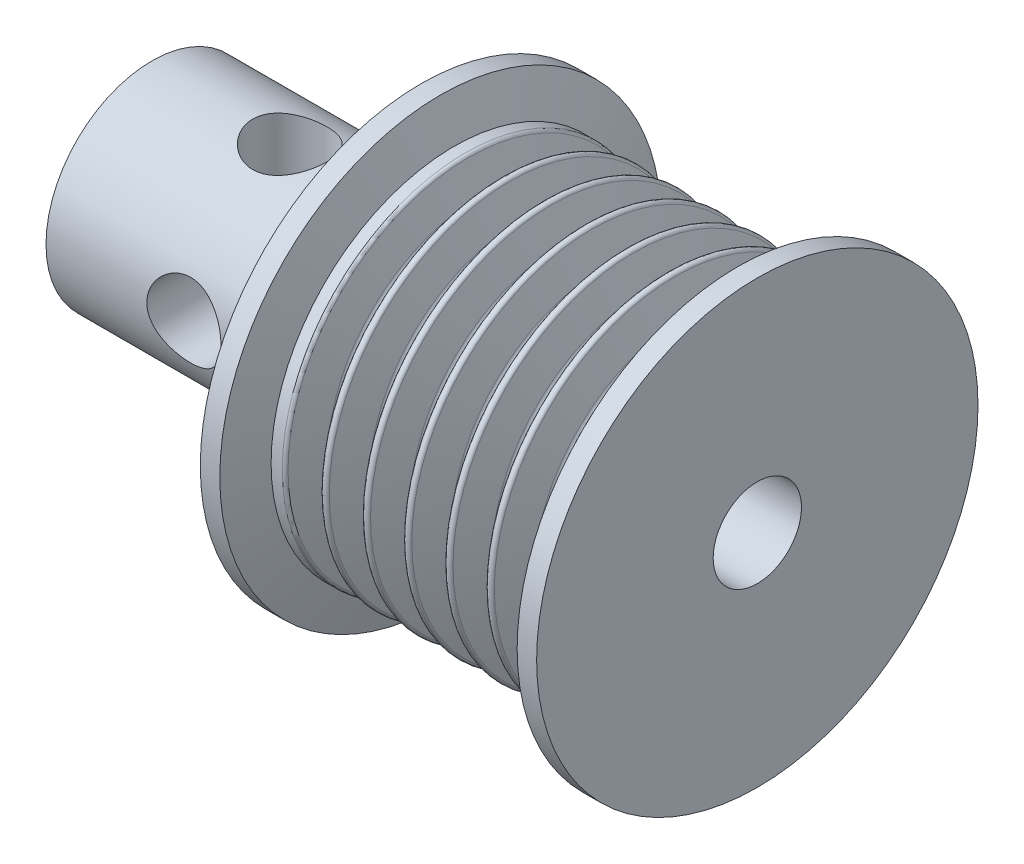
SolidWorks part; units mm, degrees
material "6061-T6 (SS)"
ref_plane "Front Plane" through (0, 0, 0) normal (0, 0, 1) x (1, 0, 0)
ref_plane "Top Plane" through (0, 0, 0) normal (0, 1, 0) x (1, 0, 0)
ref_plane "Right Plane" through (0, 0, 0) normal (1, 0, 0) x (0, 0, -1)
sketch "Sketch1" plane through (0, 0, 0) normal (0, 0, 1) x (1, 0, 0)
  line L0 (0, 0) -> (0, 2.5) construction
  line L1 (0, 2.5) -> (34.29, 2.5)
  line L2 (34.29, 2.5) -> (34.29, 12.5)
  line L3 (34.29, 12.5) -> (15.24, 12.5)
  line L4 (15.24, 12.5) -> (15.24, 6)
  line L5 (0, 0) -> (13.5959, 0) construction
  line L8 (15.24, 6) -> (0, 6)
  line L9 (0, 6) -> (0, 2.5)
  dimension "D1" = 25
  dimension "D2" = 5
  dimension "D3" = 19.05
  dimension "D6" = 12
  dimension "D7" = 15.24
revolve "Revolve1" add sketch "Sketch1" angle 360 about L5
sketch "Sketch2" plane through (0, 0, 0) normal (0, 0, 1) x (1, 0, 0)
  line L0 (29.4386, 12.5) -> (29.4386, 10.3699)
  line L1 (15.24, 6) -> (15.24, -6) construction
  line L2 (29.6295, 10.2362) -> (30.2251, 8.5999)
  line L3 (30.9889, 8.5999) -> (31.5845, 10.2362)
  line L4 (31.7754, 10.3699) -> (31.7754, 12.5)
  line L5 (31.7754, 12.5) -> (29.4386, 12.5)
  line L6 (29.4386, 11.43) -> (31.7754, 11.43) construction
  line L7 (15.24, 0) -> (34.29, 0) construction
  line L8 (29.6295, 10.2362) -> (31.5845, 10.2362) construction
  line L9 (29.4386, 12.5) -> (27.1018, 12.5) construction
  line L10 (34.29, 12.5) -> (15.24, 12.5) construction
  line L11 (27.1018, 12.5) -> (24.765, 12.5) construction
  line L13 (24.765, 0) -> (24.765, 12.5) construction
  line L15 (34.29, -12.5) -> (34.29, 12.5) construction
  arc A0 (29.4386, 10.3699) -> (29.6295, 10.2362) centre (29.4386, 10.1667) cw
  arc A1 (30.2251, 8.5999) -> (30.9889, 8.5999) centre (30.607, 8.7389) ccw
  arc A2 (31.5845, 10.2362) -> (31.7754, 10.3699) centre (31.7754, 10.1667) cw
  dimension "D1" = 0.4064
  dimension "D5" = 0.2032
  dimension "D2" = 2.3368
  dimension "D4" = 1.1938
  dimension "D6" = 40
  dimension "D7" = 11.43
revolve "Cut-Revolve1" cut sketch "Sketch2" angle 360 about L7
pattern_linear "LPattern1" count 6 spacing 2.3368 along (-1, 0, 0) of "Cut-Revolve1"
sketch "Sketch3" plane through (0, 0, 0) normal (0, 0, 1) x (1, 0, 0)
  line L0 (31.7754, 12.5) -> (33.1857, 12.5)
  line L1 (34.29, 12.5) -> (31.7754, 12.5) construction
  line L2 (33.1857, 12.5) -> (32.4104, 10.3699)
  line L3 (32.4104, 10.3699) -> (31.7754, 10.3699)
  line L4 (31.7754, 12.5) -> (31.7754, -12.5) construction
  line L5 (31.7754, 10.3699) -> (31.7754, 12.5)
  line L6 (31.7754, 10.3699) -> (31.7754, -10.3699) construction
  line L7 (30.607, 8.3325) -> (30.607, 11.4458) construction
  line L8 (24.765, 10.3699) -> (24.765, 14.7012) construction
  line L9 (17.7546, 10.3699) -> (17.7546, 12.5)
  line L10 (17.1196, 10.3699) -> (17.7546, 10.3699)
  line L11 (16.3443, 12.5) -> (17.1196, 10.3699)
  line L12 (17.7546, 12.5) -> (16.3443, 12.5)
  line L13 (0, 0) -> (26.9583, 0) construction
  arc A0 (30.2251, 8.5999) -> (30.9889, 8.5999) centre (30.607, 8.7389) ccw construction
  arc A1 (24.9559, 10.2362) -> (24.5741, 10.2362) centre (24.765, 10.1667) ccw construction
  dimension "D1" = 1.8034
  dimension "D2" = 20
revolve "Cut-Revolve2" cut sketch "Sketch3" angle 360 about L13
fillet "Fillet1" radius 0.762 1 edges at (15.24, 0, 6)
ref_plane "Plane1" through (0, 6, 0) normal (0, 1, 0) x (1, 0, 0)
sketch "Sketch6" plane through (0, 6, 0) normal (0, 1, 0) x (1, 0, 0)
  line L1 (7.811, 0) -> (0, 0) construction
  line L7 (11.24, 6) -> (11.24, -6) construction
  line L8 (14.478, 6) -> (0, 6) construction
  line L9 (0, -6) -> (14.478, -6) construction
  line L11 (15.24, 6.762) -> (15.24, -6.762) construction
  circle A0 centre (7.811, 0) radius 3.429 construction
  point P0 (7.811, 0)
  dimension "D1" = 6.858
  dimension "D2" = 4
hole_wizard "M5x0.8 Tapped Hole1" positions "Sketch6" profile "Sketch5" tap size "M5x0.8" standard "ANSI Metric" end condition up to next
sketch "Sketch5" plane through (7.811, 6, 0) normal (1, 0, 0) x (0, 0, 1)
  line L0 (0, 0) -> (0, 3.5)
  line L1 (0, 3.5) -> (2.1, 3.5)
  line L2 (2.1, 3.5) -> (2.1, 0)
  line L5 (2.1, 0) -> (0, 0)
  line L11 (0, -6.35) -> (0, 107.95) construction
  dimension "Thru Tap Drill Dia." = 4.2
  dimension "Thru Tap Drill Depth" = 3.5
pattern_circular "CirPattern1" count 2 over 90 about axis through (0, 0, 0) along (-1, 0, 0) of "M5x0.8 Tapped Hole1" reverse direction yes
equation "\"D2@Sketch1\"=5mm"
equation "\"D4@Sketch2\"=0.094in/2"
equation "\"D1@Sketch1\"=25mm"
equation "\"D3@Sketch1\"=0.75in"
equation "\"D7@Sketch2\"=0.9in/2"
equation "\"D7@Sketch1\"=0.60in"
equation "\"D2@Sketch6\"=4mm"
equation "\"D6@Sketch1\"=12mm"
